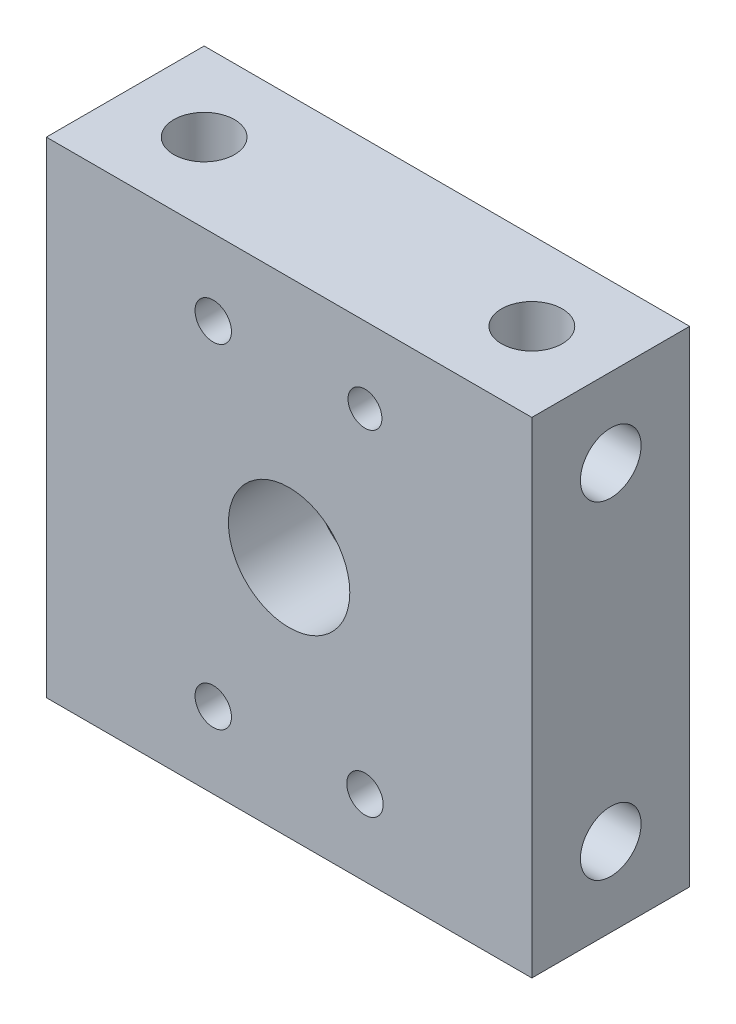
SolidWorks part; units mm, degrees
ref_plane "Front Plane" through (0, 0, 0) normal (1, 0, 0) x (0, 1, 0)
ref_plane "Top Plane" through (0, 0, 0) normal (0, 0, 1) x (0, 1, 0)
ref_plane "Right Plane" through (0, 0, 0) normal (0, 1, 0) x (-1, 0, 0)
sketch "Sketch1" plane through (0, 0, 0) normal (0, 0, 1) x (0, 1, 0)
  line L1 (-20, -20) -> (20, -20)
  line L2 (-20, -20) -> (-20, 20)
  line L3 (-20, 20) -> (20, 20)
  line L4 (20, -20) -> (20, 20)
  line L5 (-20, -20) -> (20, 20) construction
  line L6 (-20, 20) -> (20, -20) construction
  line L7 (-5, 5) -> (5, 5)
  line L8 (-5, 5) -> (-5, -5)
  line L9 (-5, -5) -> (5, -5)
  line L10 (5, 5) -> (5, -5)
  line L11 (-5, 5) -> (5, -5) construction
  line L12 (-5, -5) -> (5, 5) construction
  line L13 (5, -5) -> (-5, -5)
  line L14 (5, -5) -> (5, -13)
  line L15 (5, -13) -> (-5, -13)
  line L16 (-5, -5) -> (-5, -13)
  line L17 (-5, -13) -> (-8, -13)
  line L18 (-5, -13) -> (-5, -5)
  line L19 (-5, -5) -> (-8, -5)
  line L20 (-8, -13) -> (-8, -5)
  circle A0 centre (-10.5, 0) radius 0.9
  circle A1 centre (-10.5, 12.5) radius 0.9
  circle A2 centre (10.5, 0) radius 0.9
  circle A3 centre (10.5, 12.5) radius 0.9
  point P0 (0, 0)
  point P6 (0, 0)
  dimension "D4" = 8
  dimension "D1" = 40
  dimension "D2" = 40
  dimension "D3" = 10
  dimension "D5" = 3
extrude "Boss-Extrude1" add sketch "Sketch1" along normal blind 6 contours L1 L4 L3 L2 A2 A1 A0 L17 L20 L19 L8 L7 L10 L14 L15 A3 region at (0, -19.4343, 0)
sketch "Sketch11" plane through (0, 0, 6) normal (0, 0, 1) x (1, 0, 0)
  line L1 (-20, 20) -> (20, 20)
  line L2 (-20, 20) -> (-20, -20)
  line L3 (-20, -20) -> (20, -20)
  line L4 (20, 20) -> (20, -20)
  circle A0 centre (0, 0) radius 5
extrude "Boss-Extrude6" add sketch "Sketch11" along normal blind 7
sketch "Sketch13" plane through (0, 0, 0) normal (0, 0, -1) x (1, 0, 0)
  line L5 (-10, -17.5) -> (10, 17.5) construction
  line L6 (-10, 17.5) -> (10, -17.5) construction
  circle A0 centre (-6.25, 13.75) radius 1.5
  circle A1 centre (6.25, 13.75) radius 1.5
  circle A2 centre (6.25, -13.75) radius 1.5
  circle A3 centre (-6.25, -13.75) radius 1.5
  circle A4 centre (-6.25, 13.75) radius 3
  circle A5 centre (6.25, 13.75) radius 3
  circle A6 centre (-6.25, -13.75) radius 3
  circle A7 centre (6.25, -13.75) radius 1.3954
  circle A8 centre (6.25, -13.75) radius 3
  point P0 (0, 0)
  dimension "D1" = 20
  dimension "D2" = 35
  dimension "D3" = 2
  dimension "D4" = 2
extrude "Cut-Extrude5" cut sketch "Sketch13" against normal blind 27 contours A0 | A1 | A7 | A3 region at (-6.25, -13.75, 0) region at (6.25, -13.75, 0) region at (-6.25, 13.75, 0) region at (6.25, 13.75, 0)
extrude "Cut-Extrude6" cut sketch "Sketch13<3>" against normal blind 3 contours A6 A3 | A5 A1 | A4 A0 | A8 region at (-9.1651, -13.75, 0) region at (3.3349, -13.75, 0) region at (-9.1651, 13.75, 0)
sketch "Sketch13<3>" plane through (0, 0, 0) normal (0, 0, -1) x (1, 0, 0) same geometry as "Sketch13"
sketch "Sketch15" plane through (0, 20, 0) normal (0, 1, 0) x (-1, 0, 0)
  circle A0 centre (-13.5, 6.5) radius 2.5
  circle A1 centre (13.5, 6.5) radius 2.5
extrude "Cut-Extrude9" cut sketch "Sketch15" against normal blind 5
pattern_circular "CirPattern4" count 4 every 90 about axis through (0, 0, 13) along (0, 0, 1) of "Cut-Extrude9"
